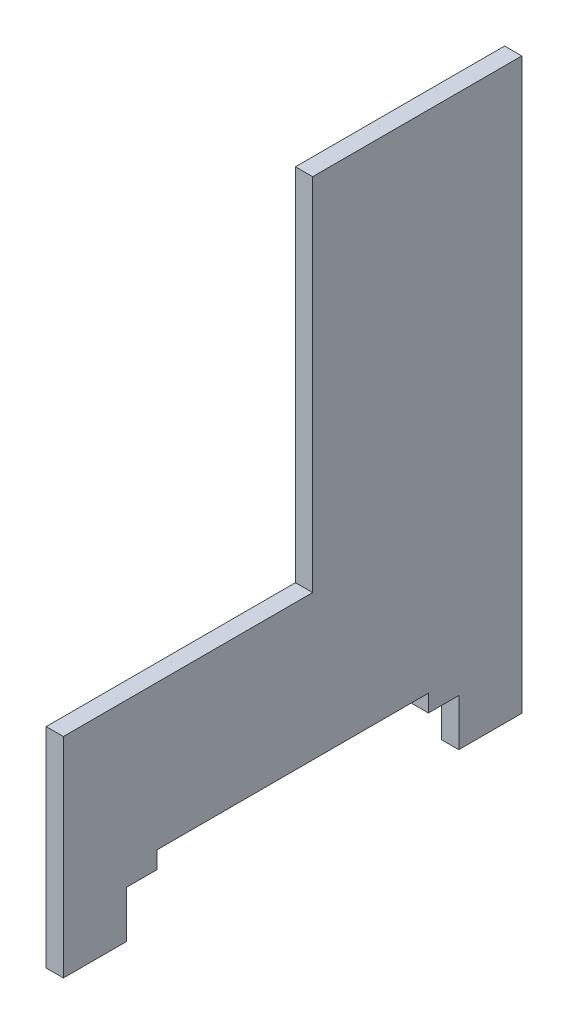
SolidWorks part; units mm, degrees
ref_plane "Front Plane" through (0, 0, 0) normal (0, 0, 1) x (1, 0, 0)
ref_plane "Top Plane" through (0, 0, 0) normal (0, 1, 0) x (1, 0, 0)
ref_plane "Right Plane" through (0, 0, 0) normal (1, 0, 0) x (0, 0, -1)
sketch "Sketch1" plane through (0, 0, 0) normal (0, 1, 0) x (1, 0, 0)
  line L0 (0, 0) -> (0, 40) construction
  line L1 (-40, 40) -> (40, 40) construction
  line L2 (-40, 40) -> (-40, -40) construction
  line L3 (-40, -40) -> (40, -40) construction
  line L4 (40, 40) -> (40, -40) construction
  line L5 (0, 0) -> (-40, 0) construction
  line L6 (-20, 60) -> (60, 60) construction
  line L7 (-37, -37) -> (37, -37) construction
  line L8 (37, 37) -> (37, -37) construction
  line L9 (-37, 37) -> (37, 37) construction
  line L10 (-37, 37) -> (-37, -37) construction
  line L11 (-37, -37) -> (-40, -37) construction
  line L12 (14.7, 20) -> (17.7, 20) construction
  line L13 (40, -32) -> (-40, -32) construction
  line L14 (-40, -29) -> (40, -29) construction
  line L15 (-40, -23.7) -> (40, -23.7) construction
  line L16 (0, -32) -> (0, -29) construction
  line L17 (0, -32) -> (0, -40) construction
  line L18 (0, -29) -> (0, -23.7) construction
  line L19 (43.7, 20) -> (49, 20) construction
  line L20 (52, 20) -> (60, 20) construction
  line L21 (40, 2.3) -> (-40, 2.3) construction
  line L22 (-40, 5.3) -> (40, 5.3) construction
  line L23 (3, 5.3) -> (3, 2.3) construction
  line L25 (40, -0.7) -> (-40, -0.7) construction
  line L26 (40, 8.3) -> (-40, 8.3) construction
  line L27 (3, 2.3) -> (3, -0.7) construction
  line L28 (3, 5.3) -> (3, 8.3) construction
  line L29 (17.7, 20) -> (20.7, 20) construction
  line L30 (19, 20) -> (56.5, 20) construction
  line L31 (3, 0) -> (0, 0) construction
  line L33 (40, 32) -> (-40, 32) construction
  line L34 (-40, 29) -> (40, 29) construction
  line L35 (-40, 23.7) -> (40, 23.7) construction
  line L36 (6, 2.3) -> (6, 1) construction
  line L37 (6, -36.5) -> (6, -40) construction
  line L38 (56.5, 20) -> (60, 20) construction
  line L40 (3, 0) -> (6, 0) construction
  line L41 (6, 1) -> (6, -36.5) construction
  line L42 (19, 20) -> (17.7, 20) construction
sketch "Sketch2" plane through (0, 0, 0) normal (1, 0, 0) x (0, 0, -1)
  line L0 (40, 0) -> (-40, 0) construction
  line L1 (40, 3.55) -> (-40, 3.55)
  line L2 (40, 3.55) -> (40, 102.907)
  line L3 (40, 102.907) -> (-40, 102.907) construction
  line L4 (-40, 3.55) -> (-40, 102.907) construction
  line L5 (40, -3.55) -> (-40, -3.55) construction
  line L6 (0, 0) -> (0, 102.907) construction
  line L7 (20, -5.5) -> (20, -47.5) construction
  line L8 (5.3, 47.5) -> (2.3, 47.5)
  line L9 (5.3, 47.5) -> (5.3, 5.5)
  line L10 (5.3, 5.5) -> (2.3, 5.5)
  line L11 (2.3, 47.5) -> (2.3, 5.5)
  line L12 (5.3, 5.5) -> (5.3, 3.55) construction
  line L13 (20, -5.5) -> (20, -3.55) construction
  line L14 (5.3, 26.5) -> (-36.5, 26.5) construction
  line L15 (20, -16.45) -> (20, -36.55) construction
  line L16 (-36.5, 36.55) -> (1, 36.55)
  line L17 (-36.5, 36.55) -> (-36.5, 16.45)
  line L18 (-36.5, 16.45) -> (1, 16.45)
  line L19 (1, 36.55) -> (1, 16.45)
  line L20 (37, 99.907) -> (37, 6.55) construction
  line L21 (37, 6.55) -> (-37, 6.55) construction
  line L22 (-37, 6.55) -> (-37, 99.907) construction
  line L23 (-37, 6.55) -> (-37, 3.55) construction
  line L24 (-37, 6.55) -> (-40, 6.55) construction
  line L25 (-23.7, 3.55) -> (-23.7, 6.55)
  line L26 (-23.7, 6.55) -> (-29, 6.55)
  line L27 (-29, 6.55) -> (-29, 11.75)
  line L28 (-29, 11.75) -> (-23.7, 11.75)
  line L29 (-23.7, 11.75) -> (-23.7, 14.75)
  line L30 (-23.7, 14.75) -> (-40, 14.75)
  line L31 (-32, 14.75) -> (-32, 3.55) construction
  line L32 (20, -6.55) -> (20, -11.75) construction
  line L33 (32, 14.75) -> (32, 3.55) construction
  line L34 (23.7, 14.75) -> (40, 14.75)
  line L35 (23.7, 11.75) -> (23.7, 14.75)
  line L36 (29, 11.75) -> (23.7, 11.75)
  line L37 (29, 6.55) -> (29, 11.75)
  line L38 (23.7, 6.55) -> (29, 6.55)
  line L39 (23.7, 3.55) -> (23.7, 6.55)
  line L40 (23.7, 14.75) -> (-23.7, 14.75) construction
  line L41 (37, 99.907) -> (-37, 99.907) construction
  line L42 (17.05, 97.907) -> (17.05, 99.907) construction
  line L43 (3.5, 102.907) -> (3.5, 40.05) construction
  line L44 (-37, 99.907) -> (-37, 102.907) construction
  line L45 (-37, 99.907) -> (-40, 99.907) construction
  line L46 (3.5, 40.05) -> (-40, 40.05)
  line L47 (6.5, 102.907) -> (6.5, 37.05) construction
  line L48 (6.5, 37.05) -> (-40, 37.05) construction
  line L49 (3.5, 40.05) -> (3.5, 37.05) construction
  line L50 (3.5, 40.05) -> (6.5, 40.05) construction
  line L51 (7, 93.707) -> (27.1, 93.707) construction
  line L52 (6.5, 37.05) -> (6.5, 3.55) construction
  line L53 (-36.5, 36.55) -> (-37, 36.55) construction
  line L54 (-36.5, 36.55) -> (-36.5, 37.05) construction
  line L55 (3.5, 37.05) -> (3.5, 3.55) construction
  line L56 (7, 93.707) -> (27.1, 93.707) construction
  line L57 (7, 93.707) -> (7, 39.407) construction
  line L58 (7, 39.407) -> (27.1, 39.407) construction
  line L59 (27.1, 93.707) -> (27.1, 39.407) construction
  line L60 (7, 39.407) -> (27.1, 39.407) construction
  line L61 (7, 46.157) -> (7, 86.957) construction
  line L62 (27.1, 46.157) -> (27.1, 86.957) construction
  line L63 (3.5, 98.4639) -> (6.5, 98.4639) construction
  line L64 (3.5, 55.3502) -> (6.5, 55.3502) construction
  circle A0 centre (17.05, 76.907) radius 21 construction
  circle A1 centre (17.05, 76.907) radius 21 construction
  circle A2 centre (17.05, 76.907) radius 24 construction
  dimension "D2" = 3
  dimension "D1" = 2
  dimension "D3" = 0.5
  dimension "D4" = 43.5
ref_plane "xslide" through (0, 26.5, 0) normal (0, 1, 0) x (1, 0, 0)
ref_plane "xgear" through (0, 0, -2.3) normal (0, 0, 1) x (1, 0, 0)
sketch "Sketch3" plane through (0, 0, 0) normal (0, 1, 0) x (1, 0, 0)
  line L0 (29, 31.8) -> (23.7, 31.8)
  line L1 (40, 40) -> (-40, 40)
  line L2 (40, 40) -> (40, -40)
  line L3 (40, -40) -> (-40, -40)
  line L4 (-40, 40) -> (-40, -40)
  line L5 (37, 37) -> (-37, 37) construction
  line L6 (37, 37) -> (37, -37) construction
  line L7 (37, -37) -> (-37, -37) construction
  line L8 (-37, 37) -> (-37, -37) construction
  line L9 (23.7, 31.8) -> (23.7, 28.8)
  line L10 (23.7, 28.8) -> (40, 28.8)
  line L11 (29, 31.8) -> (29, 37)
  line L12 (0, 0) -> (0, 40) construction
  line L13 (0, 0) -> (-40, 0) construction
  line L14 (-32, 28.8) -> (-32, 40)
  line L15 (-23.7, 28.8) -> (-40, 28.8)
  line L16 (-26.35, 31.8) -> (-26.35, 17.05) construction
  line L17 (32, 28.8) -> (32, 40)
  line L18 (-23.7, 31.8) -> (-23.7, 28.8)
  line L19 (29, 37) -> (23.7, 37)
  line L20 (23.7, 37) -> (23.7, 40)
  line L21 (29, 31.8) -> (32, 31.8) construction
  line L22 (32, 31.8) -> (40, 31.8) construction
  line L23 (37, 37) -> (40, 37) construction
  line L24 (49, 20) -> (54.2, 20) construction
  line L25 (52, 20) -> (60, 20) construction
  line L26 (49, 20) -> (43.7, 20) construction
  line L27 (-29, 31.8) -> (-23.7, 31.8)
  line L28 (-29, 31.8) -> (-29, 37)
  line L29 (-29, 37) -> (-23.7, 37)
  line L30 (-23.7, 37) -> (-23.7, 40)
  line L31 (23.7, 28.8) -> (-23.7, 28.8) construction
  line L32 (18.7, -6.95) -> (18.7, 41.05) construction
  line L33 (15.7, -3.95) -> (12.7, -3.95)
  line L34 (15.7, -3.95) -> (15.7, 38.05)
  line L35 (15.7, 38.05) -> (12.7, 38.05)
  line L36 (12.7, -3.95) -> (12.7, 38.05)
  line L38 (14.7, 20) -> (-27.3, 20) construction
  line L39 (-6.35, 20) -> (8.4, 20) construction
  line L40 (15.7, 17.05) -> (12.7, 17.05) construction
  line L41 (12.7, 17.05) -> (11.4, 17.05) construction
  line L42 (11.4, 17.05) -> (-26.1, 17.05) construction
  line L43 (19, 20) -> (17.7, 20) construction
  line L44 (19, 20) -> (56.5, 20) construction
  line L45 (56.5, 20) -> (76.6, 20) construction
  line L46 (-26.1, 7) -> (11.4, 7)
  line L47 (-26.1, 7) -> (-26.1, 27.1)
  line L48 (-26.1, 27.1) -> (11.4, 27.1)
  line L49 (11.4, 7) -> (11.4, 27.1)
  line L50 (18.7, 41.05) -> (9.7, 41.05) construction
  line L51 (9.7, -6.95) -> (9.7, 41.05) construction
  line L52 (18.7, -6.95) -> (9.7, -6.95) construction
  line L53 (15.7, 38.05) -> (18.7, 38.05) construction
  line L54 (14.7, 20) -> (11.7, 20) construction
  dimension "D1" = 5
ref_plane "zgear" through (12.7, 0, 0) normal (1, 0, 0) x (0, 0, -1)
ref_plane "zslide" through (0, 0, -17.05) normal (0, 0, 1) x (1, 0, 0)
ref_plane "zstop" through (0, 14.75, 0) normal (0, 1, 0) x (1, 0, 0)
ref_plane "peak_left" through (-40, 0, 0) normal (1, 0, 0) x (0, 0, -1)
ref_plane "peak_right" through (40, 0, 0) normal (1, 0, 0) x (0, 0, -1)
ref_plane "peak_front" through (0, 0, -40) normal (0, 0, 1) x (1, 0, 0)
ref_plane "peak_back" through (0, 0, 40) normal (0, 0, 1) x (1, 0, 0)
ref_plane "peak_uno" through (0, 0, -3.5) normal (0, 0, 1) x (1, 0, 0)
ref_plane "peak_top" through (0, 102.907, 0) normal (0, 1, 0) x (1, 0, 0)
ref_plane "peak_bottom" through (0, 3.55, 0) normal (0, 1, 0) x (1, 0, 0)
sketch "Sketch4" plane through (-40, 0, 0) normal (1, 0, 0) x (0, 0, -1)
  line L0 (40, 102.907) -> (40, 3.55)
  line L1 (40, 3.55) -> (29, 3.55)
  line L2 (29, 3.55) -> (29, 11.75)
  line L3 (29, 11.75) -> (23.7, 11.75)
  line L4 (23.7, 11.75) -> (23.7, 14.75)
  line L5 (23.7, 14.75) -> (-23.7, 14.75)
  line L6 (-23.7, 14.75) -> (-23.7, 11.75)
  line L7 (-23.7, 11.75) -> (-29, 11.75)
  line L8 (-29, 11.75) -> (-29, 3.55)
  line L9 (-29, 3.55) -> (-40, 3.55)
  line L10 (-40, 3.55) -> (-40, 40.05)
  line L11 (-40, 40.05) -> (3.5, 40.05)
  line L12 (3.5, 40.05) -> (3.5, 102.907)
  line L13 (3.5, 102.907) -> (40, 102.907)
  line L14 (40, 102.907) -> (-40, 102.907) construction
  line L15 (40, 3.55) -> (-40, 3.55) construction
  line L16 (40, 3.55) -> (40, 102.907) construction
  line L17 (-40, 3.55) -> (-40, 102.907) construction
  line L18 (3.5, 40.05) -> (-40, 40.05) construction
  line L19 (3.5, 102.907) -> (3.5, 40.05) construction
  line L20 (23.7, 14.75) -> (-23.7, 14.75) construction
  line L21 (23.7, 11.75) -> (23.7, 14.75) construction
  line L22 (-23.7, 11.75) -> (-23.7, 14.75) construction
  line L23 (-29, 6.55) -> (-29, 11.75) construction
  line L24 (29, 6.55) -> (29, 11.75) construction
  line L25 (29, 11.75) -> (23.7, 11.75) construction
  line L26 (-29, 11.75) -> (-23.7, 11.75) construction
sketch "Sketch5" plane through (0, 0, -40) normal (0, 0, 1) x (1, 0, 0)
  line L1 (-40, 102.907) -> (-37, 102.907)
  line L2 (-40, 102.907) -> (-40, 3.55)
  line L3 (-40, 3.55) -> (-37, 3.55)
  line L4 (-37, 102.907) -> (-37, 3.55)
extrude "Boss-Extrude1" add sketch "Sketch4" along normal up to vertex (3 mm away) up to point (-37, 3.55, -40)
